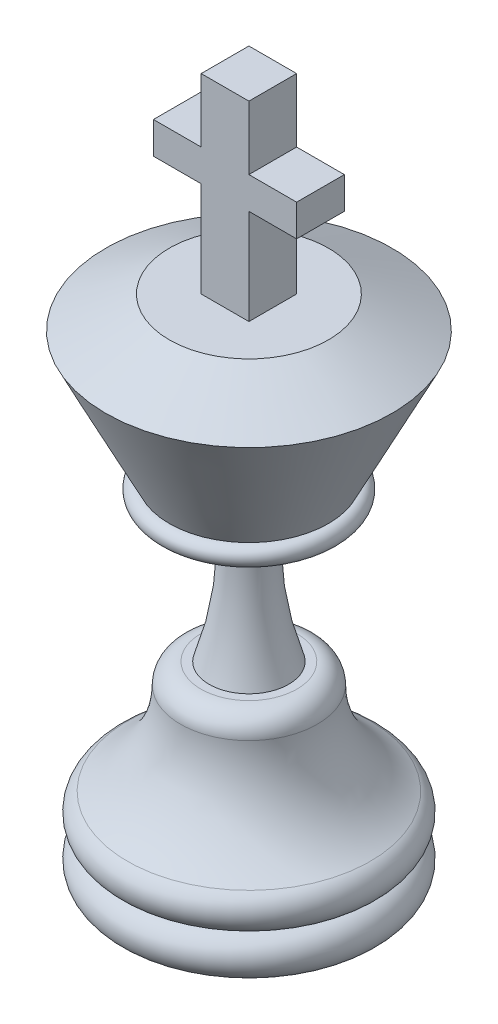
SolidWorks part; units mm, degrees
ref_plane "Front Plane" through (0, 0, 0) normal (0, 0, 1) x (1, 0, 0)
ref_plane "Top Plane" through (0, 0, 0) normal (0, 1, 0) x (1, 0, 0)
ref_plane "Right Plane" through (0, 0, 0) normal (1, 0, 0) x (0, 0, -1)
sketch "Sketch1" plane through (0, 0, 0) normal (0, 0, 1) x (1, 0, 0)
  line L0 (0, 0) -> (0, 50000) construction
  line L1 (0, 0) -> (88.9, 0)
  line L2 (0, 0) -> (0, 152.4)
  line L3 (0, 152.4) -> (38.3508, 152.4)
  line L4 (97.0058, 62.6743) -> (139.4492, 136.1884) construction
  line L5 (54.5624, 136.1884) -> (139.4492, 136.1884) construction
  arc A0 (54.5624, 136.1884) -> (97.0058, 62.6743) centre (139.4492, 136.1884) ccw
  arc A1 (88.9, 0) -> (88.9, 32.4231) centre (88.9, 16.2116) ccw
  arc A2 (88.9, 32.4231) -> (97.0058, 62.6743) centre (88.9, 48.6347) ccw
  arc A3 (38.3508, 152.4) -> (54.5624, 136.1884) centre (38.3508, 136.1884) cw
  dimension "D1" = 84.8868
  dimension "D2" = 88.9
  dimension "D3" = 152.4
  dimension "D4" = 60
revolve "Revolve2" add sketch "Sketch1" angle 360 about L2
sketch "Sketch3" plane through (0, 0, 0) normal (0, 0, 1) x (1, 0, 0)
  line L0 (0, 152.4) -> (0, 50152.4) construction
  line L1 (38.3508, 152.4) -> (-38.3508, 152.4) construction
  line L2 (0, 152.4) -> (0, 279.4)
  line L3 (0, 279.4) -> (63.5, 279.4)
  line L4 (0, 152.4) -> (31.75, 152.4)
  arc A0 (63.5, 279.4) -> (63.5, 264.16) centre (63.5, 271.78) cw
  arc A1 (63.5, 264.16) -> (19.05, 253.9206) centre (63.5, 162.56) ccw
  arc A2 (19.05, 253.9206) -> (31.75, 152.4) centre (272.271, 234.0433) ccw
  point P4 (0, 152.4)
  dimension "D1" = 101.6
  dimension "D2" = 254
  dimension "D7" = 7.62
  dimension "D3" = 38.1
  dimension "D4" = 127
  dimension "D5" = 127
  dimension "D6" = 63.5
revolve "Revolve4" add sketch "Sketch3" angle 360 about L0
sketch "Sketch4" plane through (0, 0, 0) normal (0, 0, 1) x (1, 0, 0)
  line L0 (0, 279.4) -> (0, -49720.6) construction
  line L1 (63.5, 279.4) -> (-63.5, 279.4) construction
  line L2 (0, 279.4) -> (0, 406.4)
  line L3 (0, 279.4) -> (63.5, 279.4)
  line L4 (63.5, 279.4) -> (114.3, 381)
  line L5 (0, 406.4) -> (63.5, 406.4)
  line L6 (114.3, 381) -> (63.5, 406.4)
  point P4 (0, 279.4)
  dimension "D1" = 127
  dimension "D2" = 127
  dimension "D3" = 101.6
revolve "Revolve5" add sketch "Sketch4" angle 360 about L0
sketch "Sketch5" plane through (0, 0, 0) normal (0, 0, 1) x (1, 0, 0)
  line L0 (0, 406.4) -> (0, -49593.6) construction
  line L1 (63.5, 406.4) -> (-63.5, 406.4) construction
  line L2 (19.05, 406.4) -> (19.05, 482.6)
  line L3 (19.05, 482.6) -> (57.15, 482.6)
  line L4 (57.15, 482.6) -> (57.15, 508)
  line L5 (57.15, 508) -> (19.05, 508)
  line L6 (19.05, 508) -> (19.05, 558.8)
  line L7 (19.05, 558.8) -> (-19.05, 558.8)
  line L8 (-19.05, 406.4) -> (19.05, 406.4)
  line L9 (-19.05, 508) -> (-19.05, 558.8)
  line L10 (-57.15, 508) -> (-19.05, 508)
  line L11 (-57.15, 482.6) -> (-57.15, 508)
  line L12 (-19.05, 482.6) -> (-57.15, 482.6)
  line L13 (-19.05, 406.4) -> (-19.05, 482.6)
  point P4 (0, 406.4)
  point P14 (0, 558.8)
  point P19 (0, 406.4)
  dimension "D1" = 152.4
  dimension "D2" = 25.4
  dimension "D3" = 76.2
  dimension "D4" = 38.1
  dimension "D5" = 38.1
extrude "Boss-Extrude1" add sketch "Sketch5" along normal blind 19.05 and the other way blind 19.05
